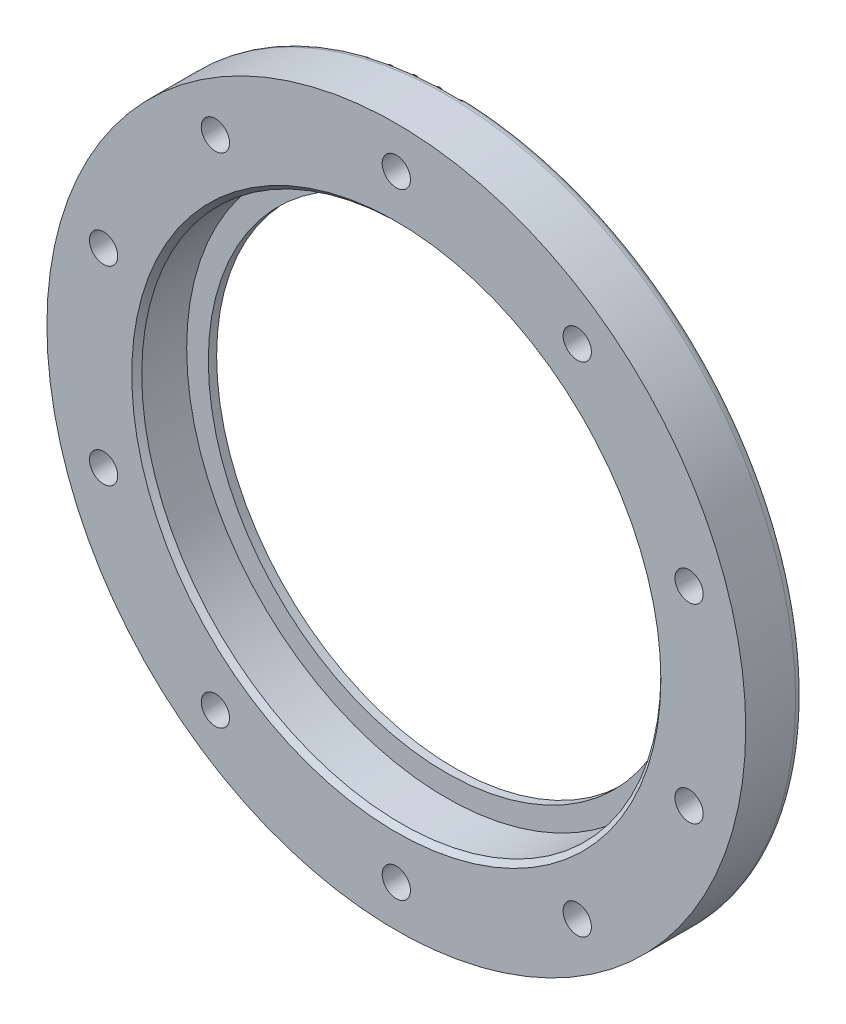
SolidWorks part; units mm, degrees
material "ABS"
ref_plane "Plan de face" through (0, 0, 0) normal (0, 0, 1) x (1, 0, 0)
ref_plane "Plan de dessus" through (0, 0, 0) normal (0, 1, 0) x (1, 0, 0)
ref_plane "Plan de droite" through (0, 0, 0) normal (1, 0, 0) x (0, 0, -1)
sketch "Esquisse1" plane through (0, 0, 0) normal (0, 0, 1) x (1, 0, 0)
  circle A0 centre (0, 0) radius 31.2
  circle A1 centre (0, 0) radius 42
  circle A2 centre (0, 0) radius 37 construction
  circle A3 centre (0, 37) radius 5 construction
  dimension "D1" = 62.4
  dimension "D2" = 10
  dimension "D3" = 74
  dimension "D4" = 84
extrude "Boss.-Extru.1" add sketch "Esquisse1" along normal blind 6
sketch "Esquisse2" plane through (0, 0, 0) normal (0, 0, -1) x (-1, 0, 0)
  circle A0 centre (0, 0) radius 28.6
  circle A1 centre (0, 0) radius 31.2 construction
  circle A2 centre (0, 0) radius 42 construction
  circle A3 centre (0, 0) radius 42
  dimension "D1" = 2.6
extrude "Boss.-Extru.2" add sketch "Esquisse2" along normal blind 1
sketch "Esquisse5" plane through (0, 0, -1) normal (0, 0, -1) x (-1, 0, 0)
  circle A0 centre (0, 0) radius 37 construction
  circle A1 centre (0, 37) radius 1.7
  circle A2 centre (21.7481, 29.9336) radius 1.7
  circle A3 centre (35.1891, 11.4336) radius 1.7
  circle A4 centre (35.1891, -11.4336) radius 1.7
  circle A5 centre (21.7481, -29.9336) radius 1.7
  circle A6 centre (0, -37) radius 1.7
  circle A7 centre (-21.7481, -29.9336) radius 1.7
  circle A8 centre (-35.1891, -11.4336) radius 1.7
  circle A9 centre (-35.1891, 11.4336) radius 1.7
  circle A10 centre (-21.7481, 29.9336) radius 1.7
  point P25 (0, 0)
  dimension "D1" = 74
  dimension "D2" = 3.4
  dimension "D3" = 10
extrude "Enlèv. mat.-Extru.1" cut sketch "Esquisse5" against normal through all
sketch "Esquisse6" plane through (0, 0, -1) normal (0, 0, -1) x (-1, 0, 0)
  circle A0 centre (0, 37) radius 3
  circle A1 centre (21.7481, 29.9336) radius 3
  circle A2 centre (35.1891, 11.4336) radius 3
  circle A3 centre (35.1891, -11.4336) radius 3
  circle A4 centre (21.7481, -29.9336) radius 3
  circle A5 centre (0, -37) radius 3
  circle A6 centre (-21.7481, -29.9336) radius 3
  circle A7 centre (-35.1891, -11.4336) radius 3
  circle A8 centre (-35.1891, 11.4336) radius 3
  circle A9 centre (-21.7481, 29.9336) radius 3
  point P23 (0, 0)
  dimension "D1" = 6
  dimension "D2" = 10
extrude "Enlèv. mat.-Extru.2" cut sketch "Esquisse6" against normal blind 3.2
chamfer "Chanfrein1" distance 0.6 angle 45 1 edges at (31.2, 0, 6)
fillet "Congé2" radius 1 1 edges at (-42, 0, -1)
